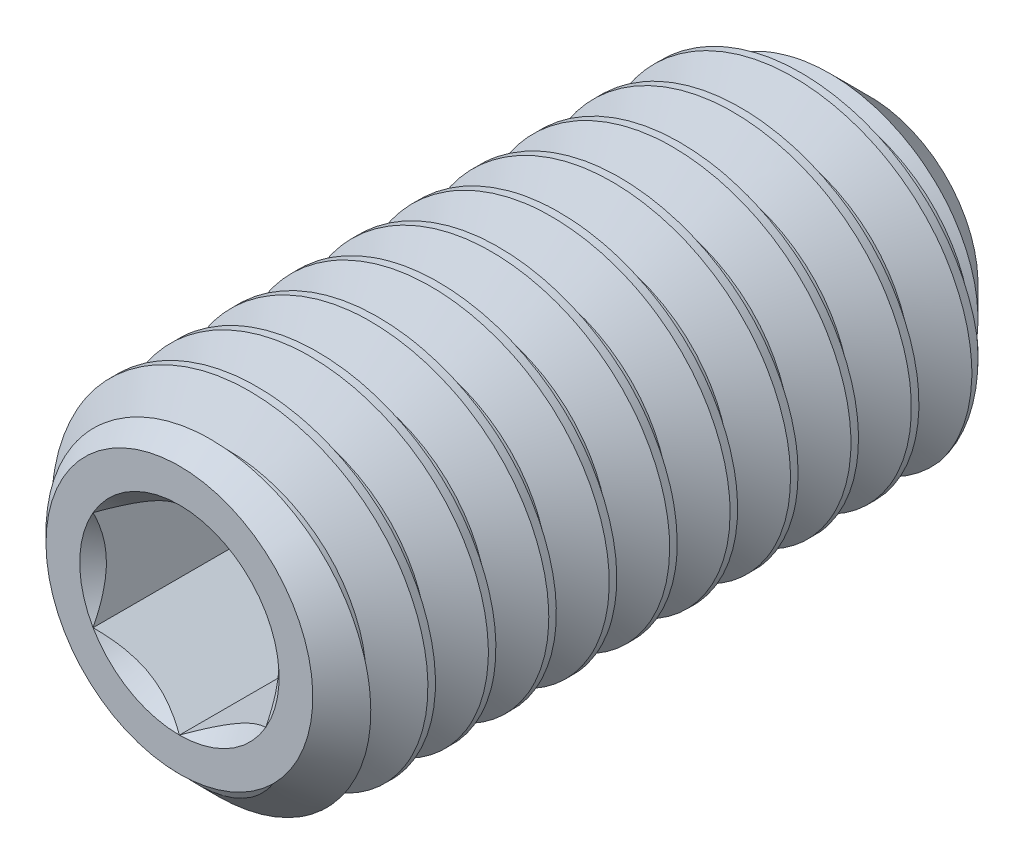
SolidWorks part; units mm, degrees
ref_plane "Front Plane" through (0, 0, 0) normal (0, 0, 1) x (1, 0, 0)
ref_plane "Top Plane" through (0, 0, 0) normal (0, 1, 0) x (1, 0, 0)
ref_plane "Right Plane" through (0, 0, 0) normal (1, 0, 0) x (0, 0, -1)
sketch "Sketch1" plane through (0, 0, 0) normal (1, 0, 0) x (0, 0, -1)
  line L0 (-4, 0) -> (4, 0) construction
  line L1 (-4, -2) -> (-4, 2) construction
  line L2 (-4, -1) -> (-4, 1) construction
  line L3 (-4, 2) -> (4, 2) construction
  line L4 (4, 2) -> (4, 0) construction
  line L5 (-4.6562, 2.0758) -> (-3.9562, 2.0758)
  line L6 (-3.9562, 2.0758) -> (-4.3062, 1.4696)
  line L7 (-4.3062, 1.4696) -> (-4.6562, 2.0758)
  line L8 (-4.3062, 1.4696) -> (-4.3062, 1.5453)
  line L9 (-4.3062, 2.0758) -> (-4.3062, 2)
  line L10 (-4.6125, 2) -> (-4, 2)
  line L11 (-4.6344, 2.0379) -> (-3.9781, 2.0379)
  line L12 (-4.35, 1.5453) -> (-4.2625, 1.5453)
  line L13 (-4, 1.5453) -> (-3.5453, 2) construction
  line L14 (-4, -1.5453) -> (-3.5453, -2) construction
  line L15 (3.25, 2) -> (4, 1.25) construction
  point P3 (-2.95, -2)
  point P4 (0, 0)
  point P8 (-4, 0)
  point P11 (-4, 0)
  point P18 (-1.5, 0)
  point P21 (-4.3062, 2)
  point P24 (-4.3062, 2.0379)
  point P27 (-4.3062, 1.5453)
  dimension "Length" = 8
  dimension "Thread Size" = 4
  dimension "Drive Size" = 2
  dimension "Thread Pitch" = 0.7
  dimension "D1" = 0.0875
  dimension "D2" = 1.05
  dimension "Drive Depth" = 2.5
  dimension "Drive Side Chamfer Angle" = 90
  dimension "Bottom Chamfer Angle" = 45
  dimension "Bottom Chamfer Diameter" = 2.5
sketch "Sketch2" plane through (0, 0, 0) normal (1, 0, 0) x (0, 0, -1)
  line L0 (3.25, 2) -> (4, 1.25) construction
  line L1 (-4, 0) -> (4, 0)
  line L2 (-4, 0) -> (-4, 1.5453)
  line L3 (-3.5453, 2) -> (3.25, 2)
  line L4 (4, 0) -> (4, 1.25)
  line L5 (-4, 1.5453) -> (-3.5453, 2) construction
  line L6 (3.25, 2) -> (4, 1.25)
  line L7 (-4, 1.5453) -> (-3.5453, 2)
revolve "Revolve1" add sketch "Sketch2" angle 360 about L1
sketch "Sketch3" plane through (0, 0, 4) normal (0, 0, 1) x (1, 0, 0)
  line L0 (0, -1) -> (0, 1) construction
  line L1 (0, 1.1547) -> (-1, 0.5774)
  line L2 (-1, 0.5774) -> (-1, -0.5774)
  line L3 (-1, -0.5774) -> (0, -1.1547)
  line L4 (0, -1.1547) -> (1, -0.5774)
  line L5 (1, -0.5774) -> (1, 0.5774)
  line L6 (1, 0.5774) -> (0, 1.1547)
  line L7 (0, -2) -> (0, 2) construction
  circle A0 centre (0, 0) radius 1 construction
extrude "Cut-Extrude1" cut sketch "Sketch3" against normal up to vertex (4 mm away) up to point (0, 0, 0)
sketch "Sketch4" plane through (0, 0, 0) normal (0, 0, 1) x (1, 0, 0)
  line L0 (-1, 0.5774) -> (-1, -0.5774) construction
  circle A0 centre (0, 0) radius 1
extrude "Cut-Extrude2" cut sketch "Sketch4" against normal through all draft 60
sketch "Sketch5" plane through (0, 0, 4) normal (0, 0, 1) x (1, 0, 0)
  line L0 (0, -2) -> (0, 2) construction
  circle A0 centre (0, 0) radius 1.1547
extrude "Cut-Extrude3" cut sketch "Sketch5" against normal blind 2.5 draft 45
sketch "Sketch6" plane through (0, 0, 4) normal (0, 0, 1) x (1, 0, 0)
  line L0 (0, -2) -> (0, 2) construction
  circle A0 centre (0, 0) radius 2
curve "Helix/Spiral1" pitch 0.7 height 8.7 radius 2 centre (0, 0, 4) axis (0, 0, -1) start towards (0, 1, 0)
sketch "Sketch7" plane through (0, 0, 0) normal (1, 0, 0) x (0, 0, -1)
  line L0 (-4.6344, 2.0379) -> (-3.9781, 2.0379)
  line L1 (-3.9781, 2.0379) -> (-4.2625, 1.5453)
  line L2 (-4.2625, 1.5453) -> (-4.35, 1.5453)
  line L3 (-4.35, 1.5453) -> (-4.6344, 2.0379)
sweep "Cut-Sweep1" cut profiles "Sketch7" path "Helix/Spiral1"
equation "\"D1@Sketch1\"=\"Thread Pitch@Sketch1\"/8"
equation "\"D1\"= \"Length@Sketch1\" * .438"
equation "\"D4@Helix/Spiral1\"=\"Thread Pitch@Sketch1\""
equation "\"D3@Helix/Spiral1\"=\"Thread Pitch@Sketch1\"+\"Length@Sketch1\""
equation "\"D2@Sketch1\"=\"Thread Pitch@Sketch1\"*1.5"
equation "\"D1@Cut-Extrude3\"=\"Drive Depth@Sketch1\""
